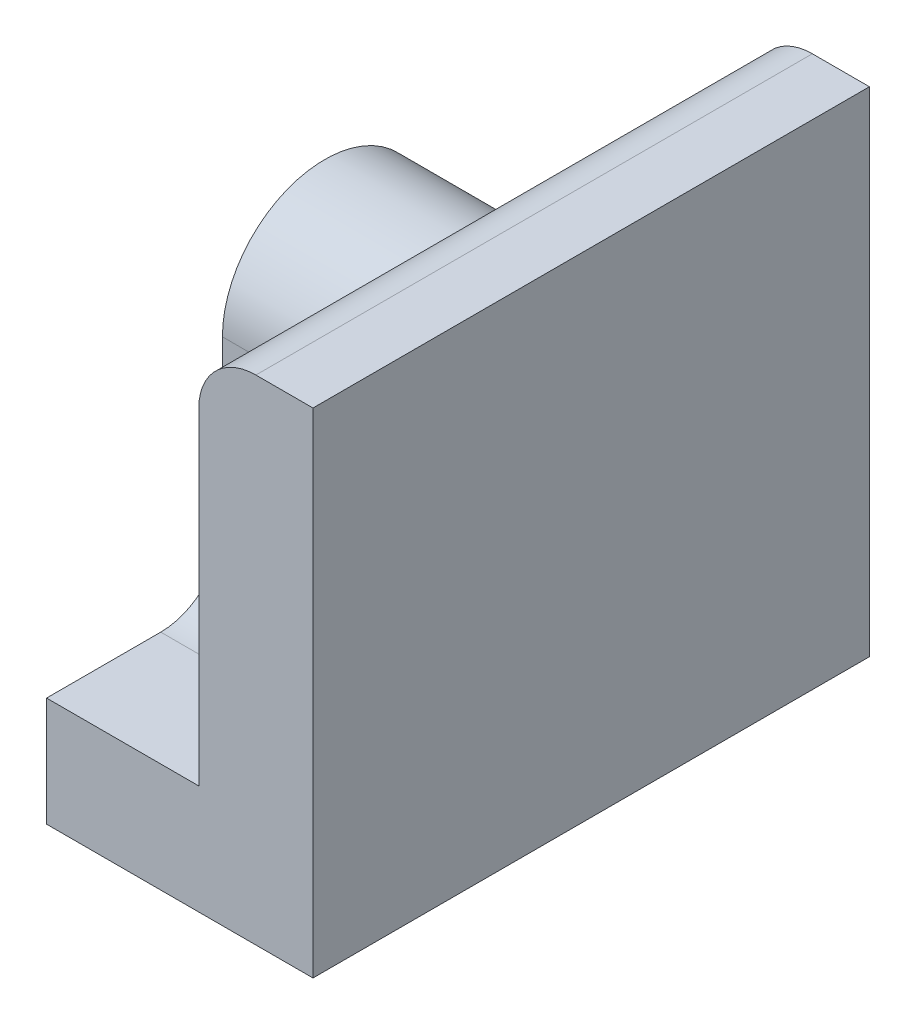
SolidWorks part; units mm, degrees
ref_plane "Front Plane" through (0, 0, 0) normal (0, 0, 1) x (1, 0, 0)
ref_plane "Top Plane" through (0, 0, 0) normal (0, 1, 0) x (1, 0, 0)
ref_plane "Right Plane" through (0, 0, 0) normal (1, 0, 0) x (0, 0, -1)
sketch "Sketch1" plane through (0, 0, 0) normal (1, 0, 0) x (0, 0, -1)
  line L5 (0, 10.1) -> (0, 0)
  line L8 (0, 10.1) -> (7.31, 10.1)
  line L9 (7.31, 0) -> (7.31, 10.1)
  line L10 (2.69, 1.62) -> (2.69, 5.91)
  line L11 (7.31, 0) -> (7.31, -2.87)
  line L12 (7.31, -2.87) -> (0, -2.87)
  line L13 (0, 55) -> (0, -55) construction
  line L14 (0, -2.87) -> (0, 0)
  line L15 (7.31, 0) -> (7.31, -2.87)
  line L16 (4.31, 0) -> (7.31, 0)
  arc A1 (2.69, 5.91) -> (0, 8.6) centre (0, 5.91) ccw
  arc A2 (2.69, 1.62) -> (4.31, 0) centre (4.31, 1.62) ccw
  dimension "D1" = 1.5
extrude "Boss-Extrude1" add sketch "Sketch1" against normal blind 7 contours A2 L10 A1 L5 region at (0, 1.3253, -2.4643)
extrude "Boss-Extrude2" add sketch "Sketch1<3>" against normal blind 3 contours L10 A2 L14 L12 L11 L9 L8 L5 A1 region at (0, 5.5254, -4.6484)
sketch "Sketch1<3>" plane through (0, 0, 0) normal (1, 0, 0) x (0, 0, -1) same geometry as "Sketch1"
mirror "Mirror1" about plane through (0, 0, 0) normal (0, 0, 1) of "Boss-Extrude2", "Boss-Extrude1"
sketch "Sketch2" plane through (0, 0, -7.31) normal (0, 0, -1) x (-1, 0, 0)
  line L0 (0, 10.1) -> (0.4393, 9.6607)
  line L1 (3, 7.1) -> (2.5607, 7.5393)
  line L2 (1.5, 10.1) -> (3, 10.1)
  line L3 (1.5, 10.1) -> (0, 10.1)
  line L4 (3, 7.1) -> (3, 10.1)
  line L5 (0, 10.1) -> (3, 10.1)
  line L6 (0, 10.1) -> (0.4393, 9.6607)
  line L7 (2.5607, 7.5393) -> (3, 7.1)
  line L8 (0.4393, 9.6607) -> (0, 10.1)
  line L9 (2.5607, 7.5393) -> (3, 7.1)
  circle A0 centre (1.5, 8.6) radius 1.5
  point P10 (0, 0)
  point P11 (0, 0)
  point P12 (0, 0)
  line M12 (3, 10.1) -> (0, 10.1)
extrude "Cut-Extrude1" cut sketch "Sketch2" along direction (0, 0, 1) on the side against the normal up to next (14.62 mm away) contours A0 L4 M12 region at (-2.6649, 9.7649, -7.31)
